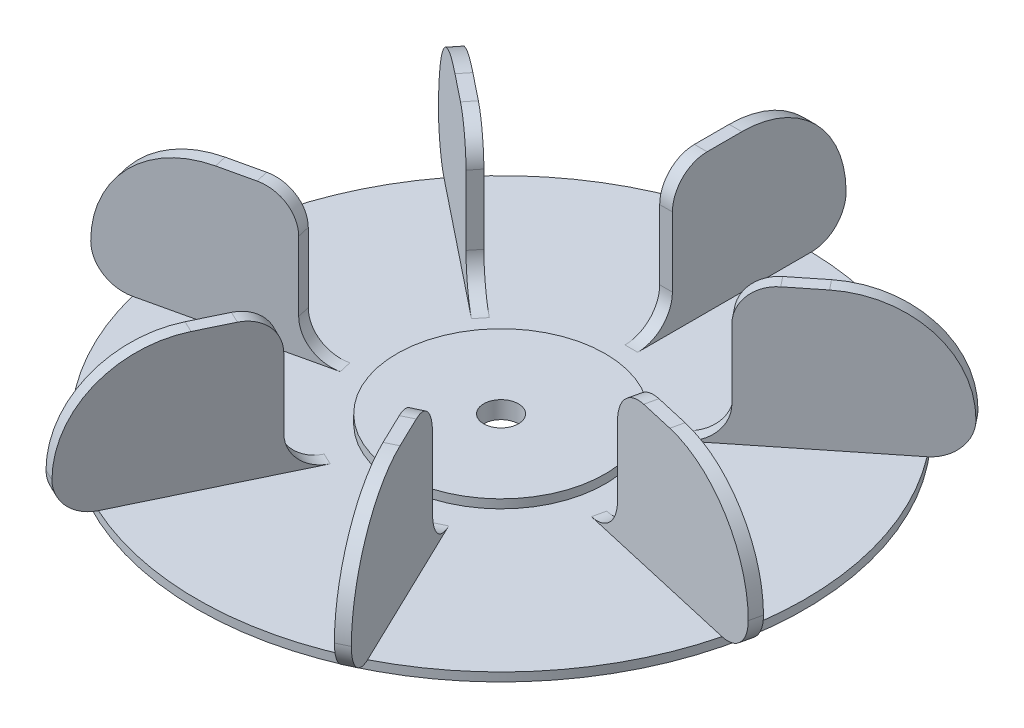
SolidWorks part; units mm, degrees
ref_plane "Front Plane" through (0, 0, 0) normal (0, 0, 1) x (1, 0, 0)
ref_plane "Top Plane" through (0, 0, 0) normal (0, 1, 0) x (1, 0, 0)
ref_plane "Right Plane" through (0, 0, 0) normal (1, 0, 0) x (0, 0, -1)
sketch "Sketch2" plane through (0, 0, 0) normal (1, 0, 0) x (0, 0, -1)
  line L0 (10, 0) -> (10, 10)
  line L1 (10, 10) -> (60, 10)
  line L2 (60, 10) -> (60, 5)
  line L3 (60, 5) -> (175, 5)
  line L4 (175, 5) -> (175, 0)
  line L5 (175, 0) -> (32.8601, 2)
  line L6 (32.8601, 2) -> (10, 0)
  line L7 (10, 0) -> (0, 0) construction
  line L8 (0, 0) -> (0, 17.2205)
  dimension "D1" = 10
  dimension "D2" = 165
  dimension "D3" = 2
  dimension "D4" = 50
  dimension "D5" = 10
  dimension "D6" = 5
  dimension "D7" = 85
revolve "Revolve2" add sketch "Sketch2" angle 360 about L8 region at (0, 4.206, -80.3079)
sketch "Sketch3" plane through (0, 5, 0) normal (0, 1, 0) x (1, 0, 0)
  line L0 (0, 0) -> (0, 145) construction
  line L2 (-3.6613, 195) -> (3.6613, 195)
  line L3 (-3.6613, 195) -> (-3.6613, 95)
  line L4 (-3.6613, 95) -> (3.6613, 95)
  line L5 (3.6613, 195) -> (3.6613, 95)
  line L6 (-3.6613, 195) -> (3.6613, 95) construction
  line L7 (-3.6613, 95) -> (3.6613, 195) construction
  circle A1 centre (0, 0) radius 175 construction
  point P3 (0, 140.0484)
  point P10 (0, 175)
  dimension "D3" = 195
  dimension "D1" = 100
  dimension "D2" = 145
extrude "Boss-Extrude1" add sketch "Sketch3" along normal blind 80
fillet "Fillet1" radius 60 1 edges at (0, 85, -195)
fillet "Fillet2" radius 20 1 edges at (0, 5, -195)
fillet "Fillet3" radius 20 1 edges at (0, 85, -95)
fillet "Fillet4" radius 20 1 edges at (0, 5, -95)
pattern_circular "CirPattern2" count 7 over 360 about axis through (0, 10, 0) along (0, -1, 0) of "Boss-Extrude1", "Fillet1", "Fillet3", "Fillet2", "Fillet4"
